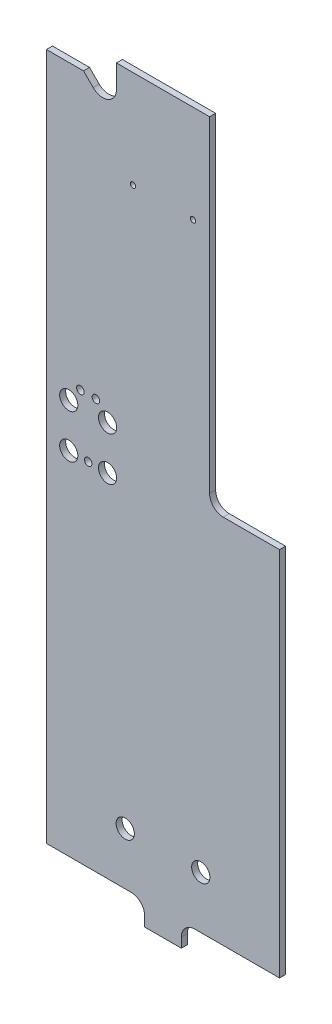
SolidWorks part; units mm, degrees
ref_plane "Front Plane" through (0, 0, 0) normal (0, 0, 1) x (1, 0, 0)
ref_plane "Top Plane" through (0, 0, 0) normal (0, 1, 0) x (1, 0, 0)
ref_plane "Right Plane" through (0, 0, 0) normal (1, 0, 0) x (0, 0, -1)
ref_axis "Axis1" through (0, 0, 0) along (0, 1, 0)
sketch "Sketch1" plane through (0, 0, 0) normal (0, 0, 1) x (1, 0, 0)
  line L0 (0, 48.006) -> (0, -48.006) construction
  line L1 (-15.24, -48.006) -> (15.24, -48.006) construction
  line L2 (-15.24, -48.006) -> (-15.24, 48.006)
  line L3 (-15.24, 48.006) -> (15.24, 48.006)
  line L4 (15.24, -48.006) -> (15.24, 48.006)
  line L5 (-15.24, 0) -> (15.24, 0) construction
  line L6 (-6.096, 48.006) -> (-6.096, 44.958)
  line L7 (-10.3885, 44.958) -> (-15.24, 44.958)
  line L8 (-2.4003, -48.006) -> (2.4003, -48.006)
  line L9 (6.096, 48.006) -> (6.096, 5.334)
  line L10 (15.24, -44.958) -> (4.1783, -44.958)
  line L11 (-2.4003, -46.736) -> (-2.4003, -48.006)
  line L12 (2.4003, -46.736) -> (2.4003, -48.006)
  line L13 (7.874, 3.556) -> (15.24, 3.556)
  line L14 (-9.1312, 43.7008) -> (-10.3885, 44.958)
  line L15 (-4.1783, -44.958) -> (-15.24, -44.958)
  circle A0 centre (-4.9403, -38.1238) radius 1.1938
  arc A1 (-4.1783, -44.958) -> (-2.4003, -46.736) centre (-4.1783, -46.736) cw
  arc A2 (4.1783, -44.958) -> (2.4003, -46.736) centre (4.1783, -46.736) ccw
  arc A3 (6.096, 5.334) -> (7.874, 3.556) centre (7.874, 5.334) ccw
  circle A5 centre (-3.9256, 35.2552) radius 0.3556
  circle A6 centre (3.9256, 35.2552) radius 0.3556
  arc A7 (-6.096, 44.958) -> (-9.1312, 43.7008) centre (-7.874, 44.958) cw
  circle A8 centre (4.9403, -38.1238) radius 1.1938
  point P14 (0, -5.4864)
  dimension "D1" = 96.012
  dimension "D2" = 1.778
  dimension "D3" = 3.048
  dimension "D7" = 5.4864
  dimension "D8" = 7.8511
  dimension "D10" = 0.7112
  dimension "D11" = 45
  dimension "D12" = 9.8806
  dimension "D13" = 2.3876
  dimension "D15" = 6.096
  dimension "D16" = 4.8006
  dimension "D4" = 30.48
  dimension "D5" = 12.192
  dimension "D6" = 44.45
  dimension "D9" = 35.2552
  dimension "D14" = 38.1238
ref_axis "Axis3" through (-4.9403, -38.1238, 0) along (0, 0, 1)
ref_plane "Back Plane" through (0, 0, -0.7874) normal (0, 0, 1) x (1, 0, 0)
ref_plane "Front Copper Render Offset" through (0, 0, 0.0254) normal (0, 0, 1) x (1, 0, 0)
ref_plane "Back Copper Render Offset" through (0, 0, -0.8128) normal (0, 0, 1) x (1, 0, 0)
ref_plane "Front Mid-Plane" through (0, 0, -0.3937) normal (0, 0, 1) x (1, 0, 0)
sketch "Sketch4" plane through (0, 0, -0.7874) normal (0, 0, 1) x (1, 0, 0)
  line L0 (0, 48.006) -> (0, -48.006) construction
  line L1 (0, 48.006) -> (0, -48.006) construction
  line L2 (0.254, -32.5882) -> (2.794, -32.5882)
  line L3 (-0.254, -32.5882) -> (-2.794, -32.5882)
  line L4 (-0.254, -32.5882) -> (-0.254, -35.1282)
  line L5 (-0.254, -35.1282) -> (-2.794, -35.1282)
  line L6 (-2.794, -32.5882) -> (-2.794, -35.1282)
  line L7 (2.794, -32.5882) -> (2.794, -35.1282)
  line L8 (0.254, -35.1282) -> (2.794, -35.1282)
  line L9 (0.254, -32.5882) -> (0.254, -35.1282)
  line L10 (-1.27, -33.8582) -> (1.27, -33.8582) construction
  line L12 (-15.24, -48.006) -> (15.24, -48.006) construction
  circle A0 centre (-1.27, -33.8582) radius 0.508 construction
  circle A1 centre (1.27, -33.8582) radius 0.508 construction
  point P14 (0, -33.8582)
  dimension "D1" = 1.016
  dimension "D5" = 14.1478
  dimension "D2" = 2.54
  dimension "D3" = 0.508
  dimension "D4" = 5.588
sketch "Sketch8" plane through (0, 0, 0) normal (0, 0, 1) x (1, 0, 0)
  line L0 (-9.7866, 0.9922) -> (-9.7866, 8.6122) construction
  line L2 (0, 48.006) -> (0, -48.006) construction
  circle A0 centre (-12.3266, 6.7072) radius 1.1875
  circle A1 centre (-12.3266, 0.9922) radius 1.1875
  circle A2 centre (-9.7866, 0.9922) radius 0.4955
  circle A3 centre (-10.8026, 8.6122) radius 0.4955
  circle A4 centre (-8.7706, 8.6122) radius 0.4955
  circle A5 centre (-7.2466, 0.9922) radius 1.1875
  circle A6 centre (-7.2466, 6.7072) radius 1.1875
  dimension "D1" = 2.375
  dimension "D2" = 0.991
  dimension "D3" = 5.715
  dimension "D4" = 2.54
  dimension "D5" = 7.62
  dimension "D6" = 1.016
  dimension "D7" = 39.116
  dimension "D8" = 9.7866
sketch "Sketch9" plane through (0, 0, 0) normal (0, 0, 1) x (1, 0, 0)
  line L0 (-0.508, -19.2262) -> (-0.508, -18.3626) construction
  line L1 (-0.635, -19.2262) -> (-0.635, -18.3626)
  line L2 (-0.381, -19.2262) -> (-0.381, -18.3626)
  line L3 (0, -0.489) -> (0, 0.489) construction
  line L4 (-8.128, -18.7944) -> (7.112, -18.7944) construction
  line L5 (-8.128, -18.7944) -> (-8.128, -3.5544) construction
  line L6 (-8.128, -3.5544) -> (7.112, -3.5544) construction
  line L7 (7.112, -18.7944) -> (7.112, -3.5544) construction
  line L8 (-8.128, -18.7944) -> (7.112, -3.5544) construction
  line L9 (-8.128, -3.5544) -> (7.112, -18.7944) construction
  arc A0 (-0.635, -19.2262) -> (-0.381, -19.2262) centre (-0.508, -19.2262) ccw
  arc A1 (-0.381, -18.3626) -> (-0.635, -18.3626) centre (-0.508, -18.3626) ccw
  point P2 (-0.508, -18.7944)
  point P7 (-0.508, -11.1744)
  dimension "D6" = 1.1176
  dimension "D1" = 0.508
  dimension "D2" = 26.9494
  dimension "D3" = 15.24
  dimension "D5" = 0.254
sketch "Sketch11" plane through (0, 0, -0.7874) normal (0, 0, 1) x (1, 0, 0)
  line L0 (2.8575, 37.6428) -> (2.8575, 38.7604) construction
  line L1 (2.6543, 37.6428) -> (2.6543, 38.7604)
  line L2 (3.0607, 37.6428) -> (3.0607, 38.7604)
  line L3 (2.8575, 36.3601) -> (-2.8575, 36.3601) construction
  line L4 (2.8575, 35.0774) -> (2.8575, 33.9598) construction
  line L5 (2.6543, 35.0774) -> (2.6543, 33.9598)
  line L6 (3.0607, 35.0774) -> (3.0607, 33.9598)
  line L7 (0, 48.006) -> (0, -48.006) construction
  arc A0 (2.6543, 37.6428) -> (3.0607, 37.6428) centre (2.8575, 37.6428) ccw
  arc A1 (3.0607, 38.7604) -> (2.6543, 38.7604) centre (2.8575, 38.7604) ccw
  arc A2 (2.6543, 35.0774) -> (3.0607, 35.0774) centre (2.8575, 35.0774) cw
  arc A3 (3.0607, 33.9598) -> (2.6543, 33.9598) centre (2.8575, 33.9598) cw
  point P2 (2.8575, 38.2016)
  point P11 (2.8575, 34.5186)
  point P18 (0, 36.3601)
  dimension "D1" = 1.524
  dimension "D3" = 5.207
  dimension "D2" = 0.4064
  dimension "D4" = 1.4986
  dimension "D5" = 5.715
sketch "Sketch14" plane through (0, 0, 0) normal (0, 0, 1) x (1, 0, 0)
  line L4 (0, -41.6798) -> (0, -34.5678) construction
  line L5 (0, -34.5678) -> (0, -27.4558) construction
  line L6 (0, -27.4558) -> (0, -20.3438) construction
  line L11 (9.8806, -41.6798) -> (9.8806, -34.5678) construction
  line L12 (0, 48.006) -> (0, -48.006) construction
  line L13 (9.8806, -34.5678) -> (9.8806, -27.4558) construction
  line L14 (9.8806, -27.4558) -> (9.8806, -20.3438) construction
  circle A0 centre (0, -41.6798) radius 2.8 construction
  circle A1 centre (9.8806, -41.6798) radius 2.8 construction
  circle A2 centre (0, -5.4864) radius 5.08 construction
  point P0 (0, -10.5664)
  point P3 (5.08, -5.4864)
  point P4 (-5.08, -5.4864)
  point P5 (12.192, -5.4864)
  point P6 (0, -0.4064)
  dimension "D1" = 5.6
  dimension "D2" = 3.556
  dimension "D4" = 10.16
  dimension "D3" = 9.8806
  dimension "D5" = 7.112
  dimension "D6" = 12.192
sketch "Sketch15" plane through (0, 0, 0) normal (0, 0, 1) x (1, 0, 0)
  line L0 (-1, -44.4798) -> (1, -44.4798) construction
  line L1 (-1, -43.9798) -> (1, -43.9798)
  line L2 (-1, -43.9798) -> (-1, -44.9798)
  line L3 (-1, -44.9798) -> (1, -44.9798)
  line L4 (1, -43.9798) -> (1, -44.9798)
  line L5 (0, -43.9798) -> (0, -44.9798) construction
  line L6 (0, 48.006) -> (0, -48.006) construction
  line L7 (7.5471, -42.599) -> (8.9614, -44.0132)
  line L8 (7.5471, -42.599) -> (6.84, -43.3061)
  line L9 (8.9614, -44.0132) -> (8.2543, -44.7203)
  line L10 (6.84, -43.3061) -> (8.2543, -44.7203)
  line L11 (7.5471, -42.599) -> (8.2543, -44.7203) construction
  line L12 (8.9614, -44.0132) -> (6.84, -43.3061) construction
  line L13 (9.8806, -41.6798) -> (7.9007, -43.6597) construction
  line L14 (9.8806, -41.6798) -> (9.8806, -34.5678) construction
  line L15 (0, -41.6798) -> (-1.9799, -43.6597) construction
  line L16 (0, -38.8798) -> (0, -44.4798) construction
  line L17 (9.8806, -38.8798) -> (9.8806, -44.4798) construction
  line L18 (-2.3, -42.6798) -> (-2.3, -40.6798)
  line L19 (-2.3, -42.6798) -> (-3.3, -42.6798)
  line L20 (-3.3, -42.6798) -> (-3.3, -40.6798)
  line L21 (-2.3, -40.6798) -> (-3.3, -40.6798)
  line L22 (-2.8, -41.6798) -> (2.8, -41.6798) construction
  line L23 (7.0806, -41.6798) -> (12.6806, -41.6798) construction
  line L24 (7.5471, -40.7605) -> (6.84, -40.0534)
  line L25 (6.84, -40.0534) -> (8.2543, -38.6392)
  line L26 (8.9614, -39.3463) -> (8.2543, -38.6392)
  line L27 (7.5471, -40.7605) -> (8.9614, -39.3463)
  line L28 (12.2141, -40.7605) -> (12.9212, -40.0534)
  line L29 (12.9212, -40.0534) -> (11.5069, -38.6392)
  line L30 (10.7998, -39.3463) -> (11.5069, -38.6392)
  line L31 (12.2141, -40.7605) -> (10.7998, -39.3463)
  line L32 (12.2141, -42.599) -> (12.9212, -43.3061)
  line L33 (12.9212, -43.3061) -> (11.5069, -44.7203)
  line L34 (10.7998, -44.0132) -> (11.5069, -44.7203)
  line L35 (12.2141, -42.599) -> (10.7998, -44.0132)
  line L36 (-1, -39.3798) -> (1, -39.3798)
  line L37 (-1, -39.3798) -> (-1, -38.3798)
  line L38 (-1, -38.3798) -> (1, -38.3798)
  line L39 (1, -39.3798) -> (1, -38.3798)
  line L40 (2.3, -42.6798) -> (3.3, -42.6798)
  line L41 (3.3, -42.6798) -> (3.3, -40.6798)
  line L42 (2.3, -40.6798) -> (3.3, -40.6798)
  line L43 (2.3, -42.6798) -> (2.3, -40.6798)
  circle A0 centre (0, -41.6798) radius 2.8 construction
  circle A1 centre (9.8806, -41.6798) radius 2.8 construction
  point P8 (0, -44.4798)
  point P16 (7.9007, -43.6597)
  dimension "D1" = 2
  dimension "D2" = 1
  dimension "D3" = 45
ref_plane "Plane1" through (0, -38.1238, 0) normal (0, 1, 0) x (0, 0, 1)
ref_plane "Plane2" through (-4.9403, 0, 0) normal (-1, 0, 0) x (0, 0, 1)
sketch "Sketch3" plane through (0, 0, 0) normal (0, 0, 1) x (1, 0, 0)
  line L0 (7.874, 3.556) -> (15.24, 3.556) construction
  line L1 (2.4003, -46.736) -> (2.4003, -48.006) construction
  line L2 (7.874, 3.556) -> (15.24, 3.556)
  line L4 (-10.3885, 44.958) -> (-15.24, 44.958) construction
  line L5 (-6.096, 48.006) -> (-6.096, 44.958) construction
  line L6 (-10.3885, 44.958) -> (-15.24, 44.958)
  line L7 (-6.096, 48.006) -> (-6.096, 44.958)
  line L8 (15.24, -48.006) -> (15.24, 48.006) construction
  line L9 (15.24, -44.958) -> (15.24, 3.556)
  line L10 (2.4003, -46.736) -> (2.4003, -48.006)
  line L11 (-2.4003, -48.006) -> (2.4003, -48.006) construction
  line L14 (15.24, -44.958) -> (4.1783, -44.958) construction
  line L15 (-2.4003, -48.006) -> (2.4003, -48.006)
  line L16 (15.24, -44.958) -> (4.1783, -44.958)
  line L20 (-15.24, 48.006) -> (15.24, 48.006) construction
  line L21 (-6.096, 48.006) -> (6.096, 48.006)
  line L22 (-2.4003, -46.736) -> (-2.4003, -48.006) construction
  line L24 (-9.1312, 43.7008) -> (-10.3885, 44.958) construction
  line L25 (-9.1312, 43.7008) -> (-10.3885, 44.958)
  line L26 (6.096, 48.006) -> (6.096, 5.334) construction
  line L27 (6.096, 48.006) -> (6.096, 5.334)
  line L28 (-2.4003, -46.736) -> (-2.4003, -48.006)
  line L29 (-4.1783, -44.958) -> (-15.24, -44.958) construction
  line L30 (-4.1783, -44.958) -> (-15.24, -44.958)
  line L31 (-15.24, -48.006) -> (-15.24, 48.006) construction
  line L32 (-15.24, -44.958) -> (-15.24, 44.958)
  arc A0 (6.096, 5.334) -> (7.874, 3.556) centre (7.874, 5.334) ccw construction
  arc A1 (6.096, 5.334) -> (7.874, 3.556) centre (7.874, 5.334) ccw
  circle A2 centre (-4.9403, -38.1238) radius 1.1938 construction
  arc A4 (4.1783, -44.958) -> (2.4003, -46.736) centre (4.1783, -46.736) ccw construction
  arc A6 (4.1783, -44.958) -> (2.4003, -46.736) centre (4.1783, -46.736) ccw
  circle A8 centre (-3.9256, 35.2552) radius 0.3556 construction
  circle A9 centre (-3.9256, 35.2552) radius 0.3556
  circle A10 centre (3.9256, 35.2552) radius 0.3556 construction
  circle A11 centre (3.9256, 35.2552) radius 0.3556
  arc A12 (-9.1312, 43.7008) -> (-6.096, 44.958) centre (-7.874, 44.958) ccw construction
  arc A13 (-9.1312, 43.7008) -> (-6.096, 44.958) centre (-7.874, 44.958) ccw
  circle A14 centre (-4.9403, -38.1238) radius 1.1938
  circle A15 centre (4.9403, -38.1238) radius 1.1938 construction
  circle A16 centre (4.9403, -38.1238) radius 1.1938
  arc A17 (-2.4003, -46.736) -> (-4.1783, -44.958) centre (-4.1783, -46.736) ccw construction
  arc A18 (-2.4003, -46.736) -> (-4.1783, -44.958) centre (-4.1783, -46.736) ccw
  circle A19 centre (-12.3266, 0.9922) radius 1.1875 construction
  circle A20 centre (-12.3266, 0.9922) radius 1.1875
  circle A21 centre (-9.7866, 0.9922) radius 0.4955 construction
  circle A22 centre (-9.7866, 0.9922) radius 0.4955
  circle A23 centre (-7.2466, 0.9922) radius 1.1875 construction
  circle A24 centre (-7.2466, 0.9922) radius 1.1875
  circle A25 centre (-7.2466, 6.7072) radius 1.1875 construction
  circle A26 centre (-7.2466, 6.7072) radius 1.1875
  circle A27 centre (-12.3266, 6.7072) radius 1.1875 construction
  circle A28 centre (-12.3266, 6.7072) radius 1.1875
  circle A29 centre (-8.7706, 8.6122) radius 0.4955 construction
  circle A30 centre (-8.7706, 8.6122) radius 0.4955
  circle A31 centre (-10.8026, 8.6122) radius 0.4955 construction
  circle A32 centre (-10.8026, 8.6122) radius 0.4955
extrude "Boss-Extrude1" add sketch "Sketch3" against normal up to surface (0.7874 mm away) up to plane "Back Plane"
sketch "Sketch13" plane through (0, 0, -0.3937) normal (0, 0, 1) x (1, 0, 0)
  line L0 (14.986, -44.704) -> (14.986, 3.302)
  line L1 (14.986, 3.302) -> (7.874, 3.302)
  line L2 (5.842, 5.334) -> (5.842, 47.752)
  line L3 (5.842, 47.752) -> (-5.842, 47.752)
  line L4 (-5.842, 47.752) -> (-5.842, 44.958)
  line L5 (-9.3108, 43.5212) -> (-10.4937, 44.704)
  line L6 (-10.4937, 44.704) -> (-14.986, 44.704)
  line L7 (-14.986, 44.704) -> (-14.986, -44.704)
  line L8 (-14.986, -44.704) -> (-4.1783, -44.704)
  line L9 (-2.1463, -46.736) -> (-2.1463, -47.752)
  line L10 (-2.1463, -47.752) -> (2.1463, -47.752)
  line L11 (2.1463, -47.752) -> (2.1463, -46.736)
  line L12 (4.1783, -44.704) -> (14.986, -44.704)
  line L13 (-2.4003, -48.006) -> (2.4003, -48.006)
  line L14 (-2.4003, -46.736) -> (-2.4003, -48.006)
  line L15 (-15.24, -44.958) -> (-4.1783, -44.958)
  line L16 (-15.24, 44.958) -> (-15.24, -44.958)
  line L17 (-10.3885, 44.958) -> (-15.24, 44.958)
  line L18 (-9.1312, 43.7008) -> (-10.3885, 44.958)
  line L19 (-6.096, 48.006) -> (-6.096, 44.958)
  line L20 (6.096, 48.006) -> (-6.096, 48.006)
  line L21 (6.096, 5.334) -> (6.096, 48.006)
  line L22 (15.24, 3.556) -> (7.874, 3.556)
  line L23 (15.24, -44.958) -> (15.24, 3.556)
  line L24 (4.1783, -44.958) -> (15.24, -44.958)
  line L25 (2.4003, -48.006) -> (2.4003, -46.736)
  line L26 (-2.4003, -48.006) -> (2.4003, -48.006) construction
  line L27 (-2.4003, -46.736) -> (-2.4003, -48.006) construction
  line L28 (-15.24, -44.958) -> (-4.1783, -44.958) construction
  line L29 (-15.24, 44.958) -> (-15.24, -44.958) construction
  line L30 (-10.3885, 44.958) -> (-15.24, 44.958) construction
  line L31 (-9.1312, 43.7008) -> (-10.3885, 44.958) construction
  line L32 (-6.096, 48.006) -> (-6.096, 44.958) construction
  line L33 (6.096, 48.006) -> (-6.096, 48.006) construction
  line L34 (6.096, 5.334) -> (6.096, 48.006) construction
  line L35 (15.24, 3.556) -> (7.874, 3.556) construction
  line L36 (15.24, -44.958) -> (15.24, 3.556) construction
  line L37 (4.1783, -44.958) -> (15.24, -44.958) construction
  line L38 (2.4003, -48.006) -> (2.4003, -46.736) construction
  arc A0 (5.842, 5.334) -> (7.874, 3.302) centre (7.874, 5.334) ccw
  circle A1 centre (3.9256, 35.2552) radius 0.3556
  circle A2 centre (3.9256, 35.2552) radius 0.3556 construction
  circle A3 centre (-3.9256, 35.2552) radius 0.3556
  circle A4 centre (-3.9256, 35.2552) radius 0.3556 construction
  circle A5 centre (-7.2466, 0.9922) radius 1.1875
  circle A6 centre (-7.2466, 0.9922) radius 1.1875 construction
  circle A7 centre (-9.7866, 0.9922) radius 0.4955
  arc A8 (-2.4003, -46.736) -> (-4.1783, -44.958) centre (-4.1783, -46.736) ccw
  arc A9 (-9.1312, 43.7008) -> (-6.096, 44.958) centre (-7.874, 44.958) ccw
  arc A10 (6.096, 5.334) -> (7.874, 3.556) centre (7.874, 5.334) ccw
  arc A11 (4.1783, -44.958) -> (2.4003, -46.736) centre (4.1783, -46.736) ccw
  arc A12 (-2.4003, -46.736) -> (-4.1783, -44.958) centre (-4.1783, -46.736) ccw construction
  arc A13 (-9.1312, 43.7008) -> (-6.096, 44.958) centre (-7.874, 44.958) ccw construction
  arc A14 (6.096, 5.334) -> (7.874, 3.556) centre (7.874, 5.334) ccw construction
  arc A15 (4.1783, -44.958) -> (2.4003, -46.736) centre (4.1783, -46.736) ccw construction
  circle A16 centre (-9.7866, 0.9922) radius 0.4955 construction
  circle A17 centre (-12.3266, 0.9922) radius 1.1875
  circle A18 centre (-12.3266, 0.9922) radius 1.1875 construction
  circle A19 centre (4.9403, -38.1238) radius 1.1938
  circle A20 centre (4.9403, -38.1238) radius 1.1938 construction
  circle A21 centre (-4.9403, -38.1238) radius 1.1938
  circle A22 centre (-4.9403, -38.1238) radius 1.1938 construction
  circle A23 centre (-10.8026, 8.6122) radius 0.4955
  circle A24 centre (-10.8026, 8.6122) radius 0.4955 construction
  circle A25 centre (-8.7706, 8.6122) radius 0.4955
  circle A26 centre (-8.7706, 8.6122) radius 0.4955 construction
  circle A27 centre (-12.3266, 6.7072) radius 1.1875
  circle A28 centre (-12.3266, 6.7072) radius 1.1875 construction
  circle A29 centre (-7.2466, 6.7072) radius 1.1875
  circle A30 centre (-7.2466, 6.7072) radius 1.1875 construction
  arc A31 (-9.3108, 43.5212) -> (-5.842, 44.958) centre (-7.874, 44.958) ccw
  arc A32 (-2.1463, -46.736) -> (-4.1783, -44.704) centre (-4.1783, -46.736) ccw
  arc A33 (4.1783, -44.704) -> (2.1463, -46.736) centre (4.1783, -46.736) ccw
  circle A34 centre (-7.2466, 0.9922) radius 1.4415
  circle A35 centre (-9.7866, 0.9922) radius 0.7495
  circle A36 centre (-12.3266, 0.9922) radius 1.4415
  circle A37 centre (-10.8026, 8.6122) radius 0.7495
  circle A38 centre (-8.7706, 8.6122) radius 0.7495
  circle A39 centre (-12.3266, 6.7072) radius 1.4415
  circle A40 centre (-7.2466, 6.7072) radius 1.4415
  circle A41 centre (3.9256, 35.2552) radius 0.6096
  circle A42 centre (-3.9256, 35.2552) radius 0.6096
  circle A43 centre (4.9403, -38.1238) radius 1.4478
  circle A44 centre (-4.9403, -38.1238) radius 1.4478
  dimension "D1" = 0
  dimension "D2" = 0
  dimension "D3" = 0
  dimension "D4" = 0
  dimension "D5" = 0
  dimension "D6" = 0
  dimension "D7" = 0
  dimension "D8" = 0
  dimension "D9" = 0
  dimension "D10" = 0
  dimension "D11" = 0
  dimension "D12" = 0
  dimension "D13" = 0.254
  dimension "D14" = 0.254
  dimension "D15" = 0.254
  dimension "D16" = 0.254
extrude "Boss-Extrude4" add sketch "Sketch13" along normal mid plane 0.254 separate body
sketch "Sketch6" plane through (0, 0, -0.7874) normal (0, 0, 1) x (1, 0, 0)
  line L0 (-0.254, -32.5882) -> (-0.254, -35.1282) construction
  line L1 (-0.254, -32.5882) -> (-2.794, -32.5882) construction
  line L2 (-2.794, -32.5882) -> (-2.794, -35.1282) construction
  line L3 (-0.254, -35.1282) -> (-2.794, -35.1282) construction
  line L4 (-0.254, -32.5882) -> (-0.254, -35.1282)
  line L5 (-0.254, -32.5882) -> (-2.794, -32.5882)
  line L6 (-2.794, -32.5882) -> (-2.794, -35.1282)
  line L7 (-0.254, -35.1282) -> (-2.794, -35.1282)
  line L8 (0.254, -32.5882) -> (0.254, -35.1282) construction
  line L9 (0.254, -32.5882) -> (2.794, -32.5882) construction
  line L10 (2.794, -32.5882) -> (2.794, -35.1282) construction
  line L11 (0.254, -35.1282) -> (2.794, -35.1282) construction
  line L12 (0.254, -32.5882) -> (0.254, -35.1282)
  line L13 (0.254, -32.5882) -> (2.794, -32.5882)
  line L14 (2.794, -32.5882) -> (2.794, -35.1282)
  line L15 (0.254, -35.1282) -> (2.794, -35.1282)
extrude "Cut-Extrude1" [suppressed] cut sketch "Sketch6" along normal blind 0.127
sketch "Sketch7" plane through (0, 0, -0.3937) normal (0, 0, 1) x (1, 0, 0)
  line L4 (0.254, -32.5882) -> (0.254, -35.1282)
  line L5 (0.254, -35.1282) -> (2.794, -35.1282)
  line L6 (2.794, -35.1282) -> (2.794, -32.5882)
  line L7 (2.794, -32.5882) -> (0.254, -32.5882)
  line L8 (0.254, -32.5882) -> (0.254, -35.1282)
  line L9 (0.254, -35.1282) -> (2.794, -35.1282)
  line L10 (2.794, -35.1282) -> (2.794, -32.5882)
  line L11 (2.794, -32.5882) -> (0.254, -32.5882)
  line L12 (-0.254, -35.1282) -> (-0.254, -32.5882)
  line L13 (-2.794, -35.1282) -> (-0.254, -35.1282)
  line L14 (-2.794, -32.5882) -> (-2.794, -35.1282)
  line L15 (-0.254, -32.5882) -> (-2.794, -32.5882)
  line L16 (-0.254, -35.1282) -> (-0.254, -32.5882)
  line L17 (-2.794, -35.1282) -> (-0.254, -35.1282)
  line L18 (-2.794, -32.5882) -> (-2.794, -35.1282)
  line L19 (-0.254, -32.5882) -> (-2.794, -32.5882)
  dimension "D1" = 0
  dimension "D2" = 0
extrude "Boss-Extrude2" [suppressed] add sketch "Sketch7" against normal up to surface (0.4191 mm away)
sketch "Sketch10" plane through (0, 0, -0.3937) normal (0, 0, 1) x (1, 0, 0)
  line L0 (-0.381, -19.2262) -> (-0.381, -18.3626) construction
  line L1 (-0.635, -19.2262) -> (-0.635, -18.3626) construction
  line L2 (-0.381, -19.2262) -> (-0.381, -18.3626)
  line L3 (-0.635, -19.2262) -> (-0.635, -18.3626)
  arc A0 (-0.635, -19.2262) -> (-0.381, -19.2262) centre (-0.508, -19.2262) ccw construction
  arc A1 (-0.381, -18.3626) -> (-0.635, -18.3626) centre (-0.508, -18.3626) ccw construction
  arc A2 (-0.635, -19.2262) -> (-0.381, -19.2262) centre (-0.508, -19.2262) ccw
  arc A3 (-0.381, -18.3626) -> (-0.635, -18.3626) centre (-0.508, -18.3626) ccw
extrude "Boss-Extrude3" [suppressed] add sketch "Sketch10" against normal up to surface (0.4191 mm away) separate body
pattern_linear "LPattern1" [suppressed] count 13 spacing 0.5 count 13 spacing 0.5 along (1, 0, 0) pattern seed only yes of bodies 101 144
ref_axis "Axis2" [suppressed] through (-0.508, -11.1744, 0) along (0, 0, 1)
pattern_circular "CirPattern1" [suppressed] count 4 over 360 about axis through (-0.508, -11.1744, 0) along (0, 0, 1) of bodies 117 141 140 139 138 137 136 135 134 133 132 131 130 129 128 127 126 125 124 123 122 121 120 119 118
combine bodies "Combine1" [suppressed] bodies to combine 144 117 118 119 120 121 122 123 124 125 126 127 128 129 130 131 132 133 134 135 136 137 138 139 140 141 142 146 147 148 149 150 151 152 153 154 155 156 157 158
sketch "Sketch12" plane through (0, 0, -0.3937) normal (0, 0, 1) x (1, 0, 0)
  line L0 (3.0607, 35.0774) -> (3.0607, 33.9598) construction
  line L1 (2.6543, 35.0774) -> (2.6543, 33.9598) construction
  line L2 (3.0607, 35.0774) -> (3.0607, 33.9598)
  line L3 (2.6543, 35.0774) -> (2.6543, 33.9598)
  line L4 (3.0607, 37.6428) -> (3.0607, 38.7604) construction
  line L5 (2.6543, 37.6428) -> (2.6543, 38.7604) construction
  line L6 (3.0607, 37.6428) -> (3.0607, 38.7604)
  line L7 (2.6543, 37.6428) -> (2.6543, 38.7604)
  line L8 (2.4257, 35.0774) -> (2.4257, 33.9598)
  line L9 (2.0193, 35.0774) -> (2.0193, 33.9598)
  line L10 (2.4257, 37.6428) -> (2.4257, 38.7604)
  line L11 (2.0193, 37.6428) -> (2.0193, 38.7604)
  line L12 (1.7907, 35.0774) -> (1.7907, 33.9598)
  line L13 (1.3843, 35.0774) -> (1.3843, 33.9598)
  line L14 (1.7907, 37.6428) -> (1.7907, 38.7604)
  line L15 (1.3843, 37.6428) -> (1.3843, 38.7604)
  line L16 (1.1557, 35.0774) -> (1.1557, 33.9598)
  line L17 (0.7493, 35.0774) -> (0.7493, 33.9598)
  line L18 (1.1557, 37.6428) -> (1.1557, 38.7604)
  line L19 (0.7493, 37.6428) -> (0.7493, 38.7604)
  line L20 (0.5207, 35.0774) -> (0.5207, 33.9598)
  line L21 (0.1143, 35.0774) -> (0.1143, 33.9598)
  line L22 (0.5207, 37.6428) -> (0.5207, 38.7604)
  line L23 (0.1143, 37.6428) -> (0.1143, 38.7604)
  line L24 (-0.1143, 35.0774) -> (-0.1143, 33.9598)
  line L25 (-0.5207, 35.0774) -> (-0.5207, 33.9598)
  line L26 (-0.1143, 37.6428) -> (-0.1143, 38.7604)
  line L27 (-0.5207, 37.6428) -> (-0.5207, 38.7604)
  line L28 (-0.7493, 35.0774) -> (-0.7493, 33.9598)
  line L29 (-1.1557, 35.0774) -> (-1.1557, 33.9598)
  line L30 (-0.7493, 37.6428) -> (-0.7493, 38.7604)
  line L31 (-1.1557, 37.6428) -> (-1.1557, 38.7604)
  line L32 (-1.3843, 35.0774) -> (-1.3843, 33.9598)
  line L33 (-1.7907, 35.0774) -> (-1.7907, 33.9598)
  line L34 (-1.3843, 37.6428) -> (-1.3843, 38.7604)
  line L35 (-1.7907, 37.6428) -> (-1.7907, 38.7604)
  line L36 (-2.0193, 35.0774) -> (-2.0193, 33.9598)
  line L37 (-2.4257, 35.0774) -> (-2.4257, 33.9598)
  line L38 (-2.0193, 37.6428) -> (-2.0193, 38.7604)
  line L39 (-2.4257, 37.6428) -> (-2.4257, 38.7604)
  line L40 (-2.6543, 35.0774) -> (-2.6543, 33.9598)
  line L41 (-3.0607, 35.0774) -> (-3.0607, 33.9598)
  line L42 (-2.6543, 37.6428) -> (-2.6543, 38.7604)
  line L43 (-3.0607, 37.6428) -> (-3.0607, 38.7604)
  line L44 (2.8575, 35.0774) -> (2.8575, 33.9598) construction
  arc A0 (3.0607, 35.0774) -> (2.6543, 35.0774) centre (2.8575, 35.0774) ccw construction
  arc A1 (2.6543, 33.9598) -> (3.0607, 33.9598) centre (2.8575, 33.9598) ccw construction
  arc A2 (3.0607, 35.0774) -> (2.6543, 35.0774) centre (2.8575, 35.0774) ccw
  arc A3 (2.6543, 33.9598) -> (3.0607, 33.9598) centre (2.8575, 33.9598) ccw
  arc A4 (2.6543, 37.6428) -> (3.0607, 37.6428) centre (2.8575, 37.6428) ccw construction
  arc A5 (3.0607, 38.7604) -> (2.6543, 38.7604) centre (2.8575, 38.7604) ccw construction
  arc A6 (2.6543, 37.6428) -> (3.0607, 37.6428) centre (2.8575, 37.6428) ccw
  arc A7 (3.0607, 38.7604) -> (2.6543, 38.7604) centre (2.8575, 38.7604) ccw
  arc A8 (2.4257, 35.0774) -> (2.0193, 35.0774) centre (2.2225, 35.0774) ccw
  arc A9 (2.0193, 33.9598) -> (2.4257, 33.9598) centre (2.2225, 33.9598) ccw
  arc A10 (2.0193, 37.6428) -> (2.4257, 37.6428) centre (2.2225, 37.6428) ccw
  arc A11 (2.4257, 38.7604) -> (2.0193, 38.7604) centre (2.2225, 38.7604) ccw
  arc A12 (1.7907, 35.0774) -> (1.3843, 35.0774) centre (1.5875, 35.0774) ccw
  arc A13 (1.3843, 33.9598) -> (1.7907, 33.9598) centre (1.5875, 33.9598) ccw
  arc A14 (1.3843, 37.6428) -> (1.7907, 37.6428) centre (1.5875, 37.6428) ccw
  arc A15 (1.7907, 38.7604) -> (1.3843, 38.7604) centre (1.5875, 38.7604) ccw
  arc A16 (1.1557, 35.0774) -> (0.7493, 35.0774) centre (0.9525, 35.0774) ccw
  arc A17 (0.7493, 33.9598) -> (1.1557, 33.9598) centre (0.9525, 33.9598) ccw
  arc A18 (0.7493, 37.6428) -> (1.1557, 37.6428) centre (0.9525, 37.6428) ccw
  arc A19 (1.1557, 38.7604) -> (0.7493, 38.7604) centre (0.9525, 38.7604) ccw
  arc A20 (0.5207, 35.0774) -> (0.1143, 35.0774) centre (0.3175, 35.0774) ccw
  arc A21 (0.1143, 33.9598) -> (0.5207, 33.9598) centre (0.3175, 33.9598) ccw
  arc A22 (0.1143, 37.6428) -> (0.5207, 37.6428) centre (0.3175, 37.6428) ccw
  arc A23 (0.5207, 38.7604) -> (0.1143, 38.7604) centre (0.3175, 38.7604) ccw
  arc A24 (-0.1143, 35.0774) -> (-0.5207, 35.0774) centre (-0.3175, 35.0774) ccw
  arc A25 (-0.5207, 33.9598) -> (-0.1143, 33.9598) centre (-0.3175, 33.9598) ccw
  arc A26 (-0.5207, 37.6428) -> (-0.1143, 37.6428) centre (-0.3175, 37.6428) ccw
  arc A27 (-0.1143, 38.7604) -> (-0.5207, 38.7604) centre (-0.3175, 38.7604) ccw
  arc A28 (-0.7493, 35.0774) -> (-1.1557, 35.0774) centre (-0.9525, 35.0774) ccw
  arc A29 (-1.1557, 33.9598) -> (-0.7493, 33.9598) centre (-0.9525, 33.9598) ccw
  arc A30 (-1.1557, 37.6428) -> (-0.7493, 37.6428) centre (-0.9525, 37.6428) ccw
  arc A31 (-0.7493, 38.7604) -> (-1.1557, 38.7604) centre (-0.9525, 38.7604) ccw
  arc A32 (-1.3843, 35.0774) -> (-1.7907, 35.0774) centre (-1.5875, 35.0774) ccw
  arc A33 (-1.7907, 33.9598) -> (-1.3843, 33.9598) centre (-1.5875, 33.9598) ccw
  arc A34 (-1.7907, 37.6428) -> (-1.3843, 37.6428) centre (-1.5875, 37.6428) ccw
  arc A35 (-1.3843, 38.7604) -> (-1.7907, 38.7604) centre (-1.5875, 38.7604) ccw
  arc A36 (-2.0193, 35.0774) -> (-2.4257, 35.0774) centre (-2.2225, 35.0774) ccw
  arc A37 (-2.4257, 33.9598) -> (-2.0193, 33.9598) centre (-2.2225, 33.9598) ccw
  arc A38 (-2.4257, 37.6428) -> (-2.0193, 37.6428) centre (-2.2225, 37.6428) ccw
  arc A39 (-2.0193, 38.7604) -> (-2.4257, 38.7604) centre (-2.2225, 38.7604) ccw
  arc A40 (-2.6543, 35.0774) -> (-3.0607, 35.0774) centre (-2.8575, 35.0774) ccw
  arc A41 (-3.0607, 33.9598) -> (-2.6543, 33.9598) centre (-2.8575, 33.9598) ccw
  arc A42 (-3.0607, 37.6428) -> (-2.6543, 37.6428) centre (-2.8575, 37.6428) ccw
  arc A43 (-2.6543, 38.7604) -> (-3.0607, 38.7604) centre (-2.8575, 38.7604) ccw
  dimension "D2" = 0.635
  dimension "D1" = 10
extrude "Boss-Extrude5" [suppressed] add sketch "Sketch12" against normal up to surface (0.4191 mm away)
sketch "Sketch16" plane through (0, 0, -0.3937) normal (0, 0, 1) x (1, 0, 0)
  circle A0 centre (0, -41.6798) radius 2.8 construction
  circle A1 centre (0, -41.6798) radius 2.8
  circle A2 centre (9.8806, -41.6798) radius 2.8 construction
  circle A3 centre (9.8806, -41.6798) radius 2.8
extrude "Boss-Extrude6" [suppressed] add sketch "Sketch16" along normal mid plane 0.254 separate body
sketch "Sketch17" plane through (0, 0, -0.3937) normal (0, 0, 1) x (1, 0, 0)
  line L0 (-1, -43.9798) -> (-1, -44.9798) construction
  line L1 (-1, -44.9798) -> (1, -44.9798) construction
  line L2 (1, -43.9798) -> (1, -44.9798) construction
  line L3 (-1, -43.9798) -> (1, -43.9798) construction
  line L4 (-1, -43.9798) -> (-1, -44.9798)
  line L5 (-1, -44.9798) -> (1, -44.9798)
  line L6 (1, -43.9798) -> (1, -44.9798)
  line L7 (-1, -43.9798) -> (1, -43.9798)
  line L8 (2.3, -42.6798) -> (3.3, -42.6798) construction
  line L9 (3.3, -42.6798) -> (3.3, -40.6798) construction
  line L10 (2.3, -40.6798) -> (3.3, -40.6798) construction
  line L11 (2.3, -42.6798) -> (2.3, -40.6798) construction
  line L12 (2.3, -42.6798) -> (3.3, -42.6798)
  line L13 (3.3, -42.6798) -> (3.3, -40.6798)
  line L14 (2.3, -40.6798) -> (3.3, -40.6798)
  line L15 (2.3, -42.6798) -> (2.3, -40.6798)
  line L16 (-1, -39.3798) -> (-1, -38.3798) construction
  line L17 (-1, -38.3798) -> (1, -38.3798) construction
  line L18 (1, -39.3798) -> (1, -38.3798) construction
  line L19 (-1, -39.3798) -> (1, -39.3798) construction
  line L20 (-1, -39.3798) -> (-1, -38.3798)
  line L21 (-1, -38.3798) -> (1, -38.3798)
  line L22 (1, -39.3798) -> (1, -38.3798)
  line L23 (-1, -39.3798) -> (1, -39.3798)
  line L24 (-2.3, -42.6798) -> (-3.3, -42.6798) construction
  line L25 (-3.3, -42.6798) -> (-3.3, -40.6798) construction
  line L26 (-2.3, -40.6798) -> (-3.3, -40.6798) construction
  line L27 (-2.3, -42.6798) -> (-2.3, -40.6798) construction
  line L28 (-2.3, -42.6798) -> (-3.3, -42.6798)
  line L29 (-3.3, -42.6798) -> (-3.3, -40.6798)
  line L30 (-2.3, -40.6798) -> (-3.3, -40.6798)
  line L31 (-2.3, -42.6798) -> (-2.3, -40.6798)
extrude "Boss-Extrude7" [suppressed] add sketch "Sketch17" along normal up to surface (0.4191 mm away)
sketch "Sketch18" plane through (0, 0, -0.3937) normal (0, 0, 1) x (1, 0, 0)
  line L0 (7.5471, -40.7605) -> (6.84, -40.0534) construction
  line L1 (7.5471, -40.7605) -> (8.9614, -39.3463) construction
  line L2 (8.9614, -39.3463) -> (8.2543, -38.6392) construction
  line L3 (6.84, -40.0534) -> (8.2543, -38.6392) construction
  line L4 (7.5471, -40.7605) -> (6.84, -40.0534)
  line L5 (7.5471, -40.7605) -> (8.9614, -39.3463)
  line L6 (8.9614, -39.3463) -> (8.2543, -38.6392)
  line L7 (6.84, -40.0534) -> (8.2543, -38.6392)
  line L8 (12.2141, -40.7605) -> (12.9212, -40.0534) construction
  line L9 (12.9212, -40.0534) -> (11.5069, -38.6392) construction
  line L10 (10.7998, -39.3463) -> (11.5069, -38.6392) construction
  line L11 (12.2141, -40.7605) -> (10.7998, -39.3463) construction
  line L12 (12.2141, -40.7605) -> (12.9212, -40.0534)
  line L13 (12.9212, -40.0534) -> (11.5069, -38.6392)
  line L14 (10.7998, -39.3463) -> (11.5069, -38.6392)
  line L15 (12.2141, -40.7605) -> (10.7998, -39.3463)
  line L16 (12.2141, -42.599) -> (12.9212, -43.3061) construction
  line L17 (12.9212, -43.3061) -> (11.5069, -44.7203) construction
  line L18 (10.7998, -44.0132) -> (11.5069, -44.7203) construction
  line L19 (12.2141, -42.599) -> (10.7998, -44.0132) construction
  line L20 (12.2141, -42.599) -> (12.9212, -43.3061)
  line L21 (12.9212, -43.3061) -> (11.5069, -44.7203)
  line L22 (10.7998, -44.0132) -> (11.5069, -44.7203)
  line L23 (12.2141, -42.599) -> (10.7998, -44.0132)
  line L24 (7.5471, -42.599) -> (6.84, -43.3061) construction
  line L25 (6.84, -43.3061) -> (8.2543, -44.7203) construction
  line L26 (8.9614, -44.0132) -> (8.2543, -44.7203) construction
  line L27 (7.5471, -42.599) -> (8.9614, -44.0132) construction
  line L28 (7.5471, -42.599) -> (6.84, -43.3061)
  line L29 (6.84, -43.3061) -> (8.2543, -44.7203)
  line L30 (8.9614, -44.0132) -> (8.2543, -44.7203)
  line L31 (7.5471, -42.599) -> (8.9614, -44.0132)
extrude "Boss-Extrude8" [suppressed] add sketch "Sketch18" along normal up to surface (0.4191 mm away)
sketch "Sketch19" [suppressed] plane through (0, 0, -0.3937) normal (0, 0, 1) x (1, 0, 0)
  line L0 (0, 48.006) -> (0, -48.006) construction
  line L1 (0, 48.006) -> (0, -48.006) construction
  point P0 (9.8806, -34.5678)
  point P1 (0, -27.4558)
  point P3 (9.8806, -20.3438)
  point P5 (5.08, -5.4864)
  point P10 (-5.08, -5.4864)
  point P11 (-9.8806, -20.3438)
  point P12 (-9.8806, -34.5678)
pattern_sketch "Sketch-Pattern1" [suppressed] of bodies 224 driven by "Sketch19"
sketch "Sketch20" [suppressed] plane through (0, 0, -0.3937) normal (0, 0, 1) x (1, 0, 0)
  line L0 (0, 48.006) -> (0, -48.006) construction
  line L1 (0, 48.006) -> (0, -48.006) construction
  point P0 (0, -34.5678)
  point P1 (9.8806, -27.4558)
  point P3 (0, -20.3438)
  point P5 (12.192, -5.4864)
  point P7 (0, -10.5664)
  point P9 (0, -0.4064)
  point P14 (-12.192, -5.4864)
  point P15 (-9.8806, -27.4558)
  point P16 (-9.8806, -41.6798)
pattern_sketch "Sketch-Pattern2" [suppressed] of bodies 225 driven by "Sketch20"
combine bodies "Combine2" [suppressed] operation type add bodies to combine 221 224 225 226 227 228 229 230 231 232 233 234 235 236 237 238 239 240 241
